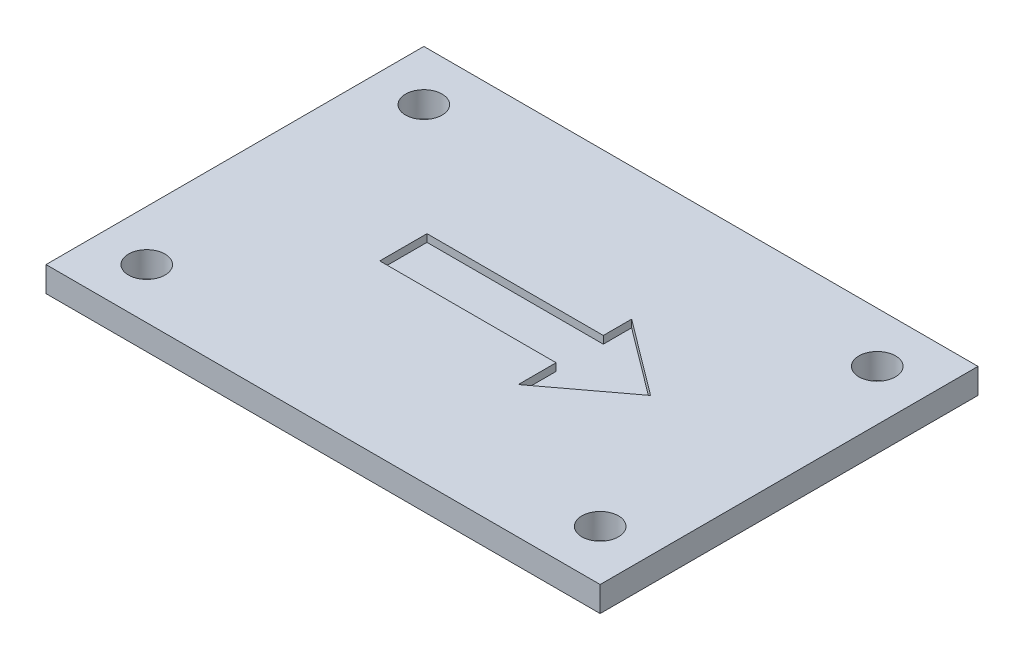
SolidWorks part; units mm, degrees
ref_plane "Front Plane" through (0, 0, 0) normal (0, 0, 1) x (1, 0, 0)
ref_plane "Top Plane" through (0, 0, 0) normal (0, 1, 0) x (1, 0, 0)
ref_plane "Right Plane" through (0, 0, 0) normal (1, 0, 0) x (0, 0, -1)
sketch "Sketch1" plane through (0, 0, 0) normal (0, 1, 0) x (1, 0, 0)
  line L1 (-22, -15) -> (22, -15)
  line L2 (-22, -15) -> (-22, 15)
  line L3 (-22, 15) -> (22, 15)
  line L4 (22, -15) -> (22, 15)
  line L5 (-22, -15) -> (22, 15) construction
  line L6 (-22, 15) -> (22, -15) construction
  point P0 (0, 0)
  dimension "D1" = 44
  dimension "D2" = 30
extrude "Lid Plate" add sketch "Sketch1" along normal blind 2
ref_plane "Lid Top" through (0, 2, 0) normal (0, 1, 0) x (1, 0, 0)
sketch "Sketch2" plane through (0, 2, 0) normal (0, 1, 0) x (1, 0, 0)
  circle A0 centre (-18, -11) radius 1.45
  circle A1 centre (-18, 11) radius 1.45
  circle A2 centre (18, -11) radius 1.45
  circle A3 centre (18, 11) radius 1.45
extrude "Clearance Holes" cut sketch "Sketch2" against normal blind 3
sketch "Sketch3" plane through (0, 2, 0) normal (0, 1, 0) x (1, 0, 0)
  line L0 (-9, -1.5) -> (5, -1.5)
  line L1 (5, -1.5) -> (5, -4.5)
  line L2 (5, -4.5) -> (11, 0)
  line L3 (-44.2539, 0) -> (44.2539, 0) construction
  line L4 (11, 0) -> (5, 4.5)
  line L5 (5, 4.5) -> (5, 2.25)
  line L6 (5, 2.25) -> (-9, 2.25)
  line L7 (-9, 2.25) -> (-9, -1.5)
extrude "Forward Arrow (+X)" cut sketch "Sketch3" against normal blind 0.6
equation "\"PodL\" = 44.0"
equation "\"PodW\" = 30.0"
equation "\"LidT\" = 2.0"
equation "\"LidInset\" = 4.0"
equation "\"ClearD\" = 2.9"
equation "\"EngraveD\" = 0.6"
equation "\"D1@Sketch1\" = \"PodL\""
equation "\"D2@Sketch1\" = \"PodW\""
equation "\"D1@Lid Plate\" = \"LidT\""
equation "\"D1@Lid Top\" = \"LidT\""
equation "\"D1@Forward Arrow (+X)\" = \"EngraveD\""
